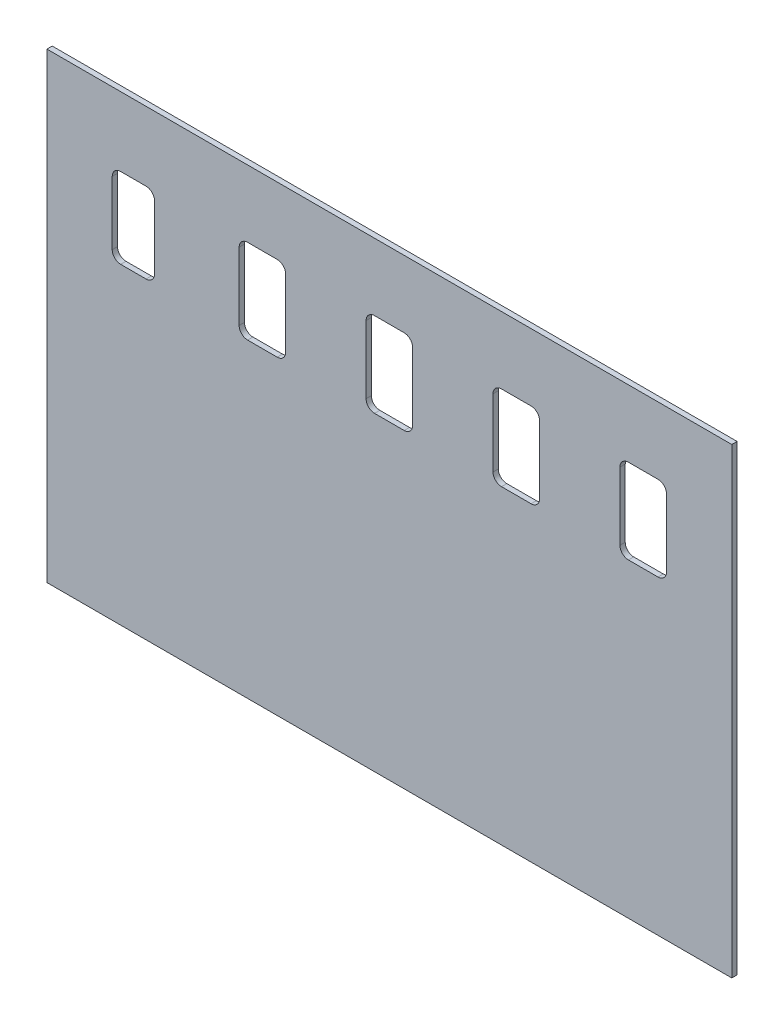
SolidWorks part; units mm, degrees
ref_plane "Front Plane" through (0, 0, 0) normal (0, 0, 1) x (1, 0, 0)
ref_plane "Top Plane" through (0, 0, 0) normal (0, 1, 0) x (1, 0, 0)
ref_plane "Right Plane" through (0, 0, 0) normal (1, 0, 0) x (0, 0, -1)
sketch "Sketch1" plane through (0, 0, 0) normal (0, 0, 1) x (1, 0, 0)
  line L1 (-205.5812, -138.684) -> (205.5812, -138.684)
  line L2 (-205.5812, -138.684) -> (-205.5812, 138.684)
  line L3 (-205.5812, 138.684) -> (205.5812, 138.684)
  line L4 (205.5812, -138.684) -> (205.5812, 138.684)
  line L5 (0, 138.684) -> (0, -138.684) construction
  line L6 (-205.5812, 0) -> (205.5813, 0) construction
  point P0 (0, 0)
  point P4 (-137.0013, 0)
  point P5 (137.0013, 0)
  point P6 (0, 97.0788)
  point P7 (0, -97.0788)
  dimension "Width" = 277.368
  dimension "Break" = 68.58
  dimension "D2" = 68.58
  dimension "D1" = 41.6052
  dimension "D3" = 41.6052
  dimension "D4" = 411.1625
sketch "Sketch2" plane through (0, 0, 0) normal (1, 0, 0) x (0, 0, -1)
  line L0 (-1.5875, -138.684) -> (1.5875, -138.684)
  dimension "Thickness" = 3.175
sketch "Sketch3" plane through (0, 0, 0) normal (0, 0, 1) x (1, 0, 0)
  line L0 (-205.5812, -138.684) -> (-205.5812, 138.684) construction
  line L1 (-205.5812, -138.684) -> (205.5812, -138.684) construction
  line L2 (205.5812, -138.684) -> (205.5812, 138.684) construction
  line L3 (-205.5812, 138.684) -> (205.5812, 138.684) construction
  line L4 (-205.5812, -138.684) -> (-205.5812, 138.684)
  line L5 (-205.5812, -138.684) -> (205.5812, -138.684)
  line L6 (205.5812, -138.684) -> (205.5812, 138.684)
  line L7 (-205.5812, 138.684) -> (205.5812, 138.684)
extrude "Boss-Extrude1" add sketch "Sketch3" along normal mid plane 3.175
sketch "Sketch4" plane through (0, 0, 1.5875) normal (0, 0, 1) x (1, 0, 0)
  line L0 (-227.6475, 73.0327) -> (-161.29, 73.0327) construction
  line L1 (-82.55, 73.0327) -> (-82.55, 98.4327) construction
  line L2 (-82.55, 98.4327) -> (-90.17, 98.4327) construction
  line L3 (-161.29, 73.0327) -> (-161.29, 97.1627) construction
  line L6 (-227.6475, -105.791) -> (-227.6475, 52.959) construction
  line L7 (-227.6475, -115.316) -> (-227.6475, 138.684) construction
  line L8 (-161.29, 73.0327) -> (-82.55, 73.0327) construction
  line L9 (-82.55, 73.0327) -> (-6.35, 73.0327) construction
  line L10 (-6.35, 73.0327) -> (69.85, 73.0327) construction
  line L11 (69.85, 73.0327) -> (146.05, 73.0327) construction
  line L12 (-82.55, 73.0327) -> (-82.55, 47.6327) construction
  line L13 (-82.55, 47.6327) -> (-62.23, 47.6327) construction
  line L16 (-161.29, 97.1627) -> (-166.37, 97.1627) construction
  line L17 (-161.29, 73.0327) -> (-161.29, 48.9027) construction
  line L18 (-161.29, 48.9027) -> (-140.97, 48.9027) construction
  line L19 (-6.35, 73.0327) -> (-6.35, 98.4327) construction
  line L24 (-6.35, 98.4327) -> (-13.97, 98.4327) construction
  line L25 (-6.35, 73.0327) -> (-6.35, 47.6327) construction
  line L26 (-6.35, 47.6327) -> (13.97, 47.6327) construction
  line L27 (69.85, 73.0327) -> (69.85, 98.4327) construction
  line L28 (-8.89, 98.4327) -> (8.89, 98.4327)
  line L29 (-13.97, 93.3527) -> (-13.97, 52.7127)
  line L30 (-8.89, 47.6327) -> (8.89, 47.6327)
  line L31 (13.97, 93.3527) -> (13.97, 52.7127)
  line L32 (69.85, 98.4327) -> (62.23, 98.4327) construction
  line L33 (69.85, 73.0327) -> (69.85, 47.6327) construction
  line L34 (69.85, 47.6327) -> (90.17, 47.6327) construction
  line L35 (146.05, 73.0327) -> (146.05, 98.4327) construction
  line L36 (67.31, 98.4327) -> (85.09, 98.4327)
  line L37 (62.23, 93.3527) -> (62.23, 52.7127)
  line L38 (67.31, 47.6327) -> (85.09, 47.6327)
  line L39 (90.17, 93.3527) -> (90.17, 52.7127)
  line L40 (146.05, 98.4327) -> (138.43, 98.4327) construction
  line L41 (146.05, 73.0327) -> (146.05, 47.6327) construction
  line L42 (146.05, 47.6327) -> (166.37, 47.6327) construction
  line L43 (-205.5812, 138.684) -> (-205.5812, 73.0327) construction
  line L44 (143.51, 98.4327) -> (161.29, 98.4327)
  line L45 (138.43, 93.3527) -> (138.43, 52.7127)
  line L46 (143.51, 47.6327) -> (161.29, 47.6327)
  line L47 (166.37, 93.3527) -> (166.37, 52.7127)
  line L48 (-85.09, 98.4327) -> (-67.31, 98.4327)
  line L49 (-90.17, 93.3527) -> (-90.17, 52.7127)
  line L50 (-85.09, 47.6327) -> (-67.31, 47.6327)
  line L51 (-62.23, 93.3527) -> (-62.23, 52.7127)
  line L53 (-161.29, 97.1627) -> (-146.05, 97.1627)
  line L54 (-166.37, 92.0827) -> (-166.37, 53.9827)
  line L55 (-161.29, 48.9027) -> (-146.05, 48.9027)
  line L56 (-140.97, 92.0827) -> (-140.97, 53.9827)
  arc A0 (138.43, 52.7127) -> (143.51, 47.6327) centre (143.51, 52.7127) ccw
  arc A1 (166.37, 52.7127) -> (161.29, 47.6327) centre (161.29, 52.7127) cw
  arc A2 (161.29, 98.4327) -> (166.37, 93.3527) centre (161.29, 93.3527) cw
  arc A3 (138.43, 93.3527) -> (143.51, 98.4327) centre (143.51, 93.3527) cw
  arc A4 (62.23, 52.7127) -> (67.31, 47.6327) centre (67.31, 52.7127) ccw
  arc A5 (90.17, 52.7127) -> (85.09, 47.6327) centre (85.09, 52.7127) cw
  arc A6 (85.09, 98.4327) -> (90.17, 93.3527) centre (85.09, 93.3527) cw
  arc A7 (67.31, 98.4327) -> (62.23, 93.3527) centre (67.31, 93.3527) ccw
  arc A8 (-13.97, 52.7127) -> (-8.89, 47.6327) centre (-8.89, 52.7127) ccw
  arc A9 (13.97, 52.7127) -> (8.89, 47.6327) centre (8.89, 52.7127) cw
  arc A10 (8.89, 98.4327) -> (13.97, 93.3527) centre (8.89, 93.3527) cw
  arc A11 (-8.89, 98.4327) -> (-13.97, 93.3527) centre (-8.89, 93.3527) ccw
  arc A19 (-90.17, 52.7127) -> (-85.09, 47.6327) centre (-85.09, 52.7127) ccw
  arc A20 (-62.23, 52.7127) -> (-67.31, 47.6327) centre (-67.31, 52.7127) cw
  arc A21 (-67.31, 98.4327) -> (-62.23, 93.3527) centre (-67.31, 93.3527) cw
  arc A22 (-85.09, 98.4327) -> (-90.17, 93.3527) centre (-85.09, 93.3527) ccw
  arc A23 (-166.37, 53.9827) -> (-161.29, 48.9027) centre (-161.29, 53.9827) ccw
  arc A24 (-146.05, 48.9027) -> (-140.97, 53.9827) centre (-146.05, 53.9827) ccw
  arc A25 (-146.05, 97.1627) -> (-140.97, 92.0827) centre (-146.05, 92.0827) cw
  arc A26 (-161.29, 97.1627) -> (-166.37, 92.0827) centre (-161.29, 92.0827) ccw
  point P16 (-76.2, 98.4327)
  point P17 (-90.17, 73.0327)
  point P18 (-13.97, 73.0327)
  point P95 (62.23, 73.0327)
  point P96 (138.43, 73.0327)
  point P97 (0, 98.4327)
  point P98 (76.2, 98.4327)
  point P99 (152.4, 98.4327)
  dimension "D1" = 5.08
  dimension "D2" = 5.08
  dimension "D5" = 5.08
  dimension "D9" = 27.94
  dimension "D10" = 27.94
  dimension "D11" = 27.94
  dimension "D12" = 27.94
  dimension "D3" = 76.2
  dimension "D4" = 76.2
  dimension "D6" = 152.4
  dimension "D7" = 65.6513
extrude "Cut-Extrude1" cut sketch "Sketch4" against normal blind 25.4 contours L53 A26 L54 A23 L55 A24 L56 A25 | A22 L48 A21 L51 A20 L50 A19 L49 | L29 A8 L30 A9 L31 A10 L28 A11 | L37 A4 L38 A5 L39 A6 L36 A7 | A3 L44 A2 L47 A1 L46 A0 L45 region at (-153.67, 73.0327, 1.5875)
equation "\"D1@Boss-Extrude1\" = \"Thickness@Sketch2\""
equation "\"D2@Sketch1\" = \"Break@Sketch1\""
equation "\"D1@Sketch1\"=\"Width@Sketch1\"*0.15"
equation "\"D3@Sketch1\"=\"D1@Sketch1\""
equation "\"SlotWidth\"= 1.1in"
equation "\"D9@Sketch4\"=\"SlotWidth\""
equation "\"D10@Sketch4\"=\"SlotWidth\""
equation "\"D11@Sketch4\"=\"SlotWidth\""
equation "\"D12@Sketch4\"=\"SlotWidth\""
